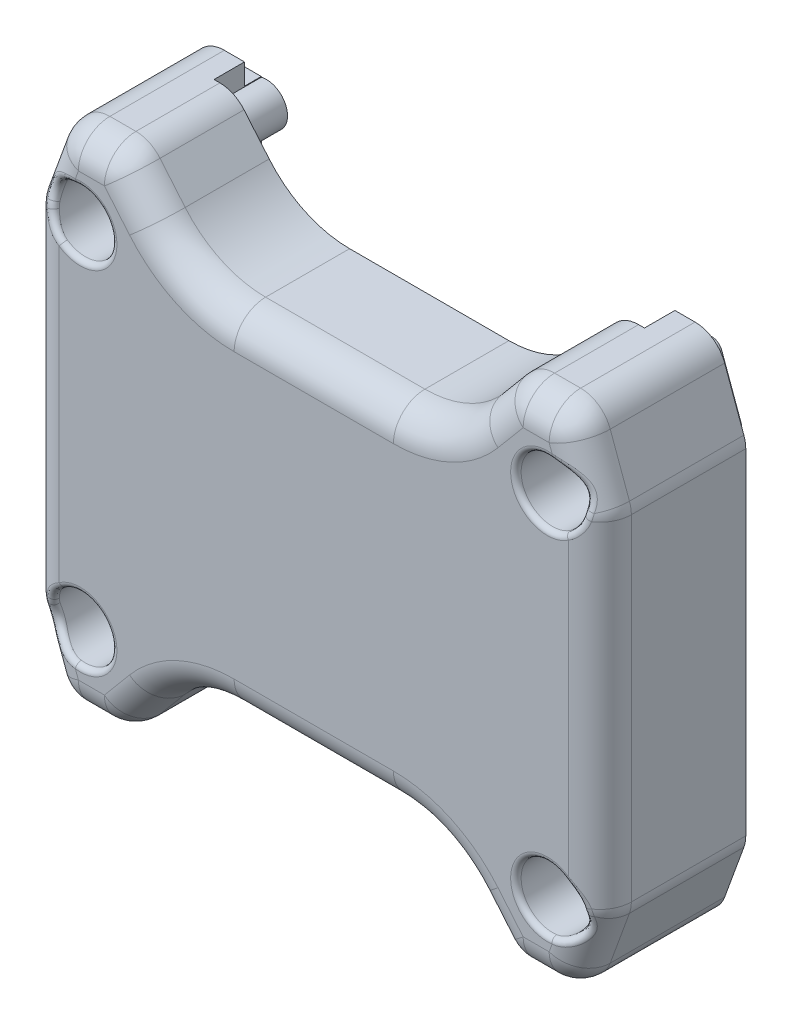
SolidWorks part; units mm, degrees
ref_plane "Alzado" through (0, 0, 0) normal (0, 0, 1) x (1, 0, 0)
ref_plane "Planta" through (0, 0, 0) normal (0, 1, 0) x (1, 0, 0)
ref_plane "Vista lateral" through (0, 0, 0) normal (1, 0, 0) x (0, 0, -1)
sketch "Croquis2" plane through (0, 0, 0) normal (0, 0, 1) x (1, 0, 0)
  line L0 (-20, 7.75) -> (-20, 15.75)
  line L1 (-20, -41.25) -> (20, -41.25)
  line L2 (-20, -41.25) -> (-20, -24.25)
  line L3 (-20, 38.75) -> (20, 38.75)
  line L4 (20, -41.25) -> (20, -24.25)
  line L5 (-20, 7.75) -> (5, 7.75)
  line L6 (-20, 4.75) -> (5, 4.75)
  line L7 (5, 7.75) -> (5, 4.75)
  line L8 (20, -10.25) -> (-5, -10.25)
  line L9 (20, -7.25) -> (-5, -7.25)
  line L10 (-5, -10.25) -> (-5, -7.25)
  line L11 (20, -7.25) -> (20, 15.75)
  line L12 (0, 38.75) -> (0, -41.25) construction
  line L14 (-20, 21.75) -> (-20, 38.75)
  line L15 (20, 21.75) -> (20, 38.75)
  line L16 (-20, -21.25) -> (20, -21.25) construction
  line L17 (-20, -18.25) -> (-20, 4.75)
  line L18 (20, -18.25) -> (20, -10.25)
  line L19 (0, 15.25) -> (0, -17.75) construction
  line L24 (27.25, -1.25) -> (-27.25, -1.25) construction
  line L29 (0, 15.25) -> (0, -17.75) construction
  line L39 (22.4196, 22.75) -> (21, 22.75)
  line L40 (21, 22.75) -> (21, 21.75)
  line L41 (21, 21.75) -> (22.4196, 21.75)
  line L42 (24.299, 20.434) -> (26.25, 15.0737)
  line L43 (26.25, 15.0737) -> (26.25, -17.5737)
  line L44 (26.25, -17.5737) -> (24.299, -22.934)
  line L45 (22.4196, -24.25) -> (21, -24.25)
  line L46 (21, -24.25) -> (21, -25.25)
  line L47 (21, -25.25) -> (22.4196, -25.25)
  line L48 (25.2387, -23.2761) -> (27.0691, -18.2471)
  line L49 (27.25, -17.221) -> (27.25, 14.721)
  line L50 (27.0691, 15.7471) -> (25.2387, 20.7761)
  line L51 (-22.4196, -25.25) -> (-21, -25.25)
  line L52 (-21, -25.25) -> (-21, -24.25)
  line L53 (-21, -24.25) -> (-22.4196, -24.25)
  line L54 (-24.299, -22.934) -> (-26.25, -17.5737)
  line L55 (-26.25, -17.5737) -> (-26.25, 15.0737)
  line L56 (-26.25, 15.0737) -> (-24.299, 20.434)
  line L57 (-22.4196, 21.75) -> (-21, 21.75)
  line L58 (-21, 21.75) -> (-21, 22.75)
  line L59 (-21, 22.75) -> (-22.4196, 22.75)
  line L60 (-25.2387, 20.7761) -> (-27.0691, 15.7471)
  line L61 (-27.25, 14.721) -> (-27.25, -17.221)
  line L62 (-27.0691, -18.2471) -> (-25.2387, -23.2761)
  line L63 (-21, 22.75) -> (-21, 21.75)
  line L64 (-21, 21.75) -> (-22.4196, 21.75)
  line L65 (-24.299, 20.434) -> (-26.25, 15.0737)
  line L66 (-26.25, 15.0737) -> (-26.25, -17.5737)
  line L67 (-26.25, -17.5737) -> (-24.299, -22.934)
  line L68 (-22.4196, -24.25) -> (-21, -24.25)
  line L69 (-21, -24.25) -> (-21, -25.25)
  line L70 (-21, -25.25) -> (-19.9422, -25.25)
  line L71 (-17.644, -24.1784) -> (-15.2474, -21.3221)
  line L72 (-7.5869, -17.75) -> (7.5869, -17.75)
  line L73 (15.2474, -21.3221) -> (17.644, -24.1784)
  line L74 (19.9422, -25.25) -> (21, -25.25)
  line L75 (21, -25.25) -> (21, -24.25)
  line L76 (21, -24.25) -> (22.4196, -24.25)
  line L77 (24.299, -22.934) -> (26.25, -17.5737)
  line L78 (26.25, -17.5737) -> (26.25, 15.0737)
  line L79 (26.25, 15.0737) -> (24.299, 20.434)
  line L80 (22.4196, 21.75) -> (21, 21.75)
  line L81 (21, 21.75) -> (21, 22.75)
  line L82 (21, 22.75) -> (19.9422, 22.75)
  line L83 (17.644, 21.6784) -> (15.2474, 18.8221)
  line L84 (7.5869, 15.25) -> (-7.5869, 15.25)
  line L85 (-15.2474, 18.8221) -> (-17.644, 21.6784)
  line L86 (-19.9422, 22.75) -> (-21, 22.75)
  line L87 (-20, -41.25) -> (20, -41.25)
  line L88 (-20, -41.25) -> (-20, -24.25)
  line L89 (-5, -10.25) -> (-5, -7.25)
  line L90 (20, -7.25) -> (-5, -7.25)
  line L91 (20, -10.25) -> (-5, -10.25)
  line L92 (5, 7.75) -> (5, 4.75)
  line L93 (-20, 4.75) -> (5, 4.75)
  line L94 (-20, 7.75) -> (5, 7.75)
  line L95 (-20, 7.75) -> (-20, 15.75)
  line L96 (20, -7.25) -> (20, 15.75)
  line L97 (20, -18.25) -> (20, -10.25)
  line L98 (20, -41.25) -> (20, -24.25)
  line L99 (-20, -18.25) -> (-20, 4.75)
  line L100 (-20, 21.75) -> (-20, 38.75)
  line L101 (-20, 38.75) -> (20, 38.75)
  line L102 (20, 21.75) -> (20, 38.75)
  line L103 (-27.0691, -18.2471) -> (-25.2387, -23.2761)
  line L104 (-27.25, 14.721) -> (-27.25, -17.221)
  line L105 (-25.2387, 20.7761) -> (-27.0691, 15.7471)
  line L106 (-21, 21.75) -> (-22.4196, 21.75)
  line L107 (-22.4196, -24.25) -> (-21, -24.25)
  line L108 (-21, -24.25) -> (-21, -25.25)
  line L109 (-21, 22.75) -> (-21, 21.75)
  line L110 (-26.25, 15.0737) -> (-26.25, -17.5737)
  line L111 (-24.299, 20.434) -> (-26.25, 15.0737)
  line L112 (-19.9422, 22.75) -> (-22.4196, 22.75)
  line L113 (-22.4196, -25.25) -> (-19.9422, -25.25)
  line L114 (-26.25, -17.5737) -> (-24.299, -22.934)
  line L115 (27.0691, 15.7471) -> (25.2387, 20.7761)
  line L116 (27.25, -17.221) -> (27.25, 14.721)
  line L117 (25.2387, -23.2761) -> (27.0691, -18.2471)
  line L118 (21, -24.25) -> (22.4196, -24.25)
  line L119 (26.25, 15.0737) -> (24.299, 20.434)
  line L120 (22.4196, 21.75) -> (21, 21.75)
  line L121 (21, 21.75) -> (21, 22.75)
  line L122 (21, -25.25) -> (21, -24.25)
  line L123 (22.4196, 22.75) -> (19.9422, 22.75)
  line L124 (26.25, -17.5737) -> (26.25, 15.0737)
  line L125 (24.299, -22.934) -> (26.25, -17.5737)
  line L126 (19.9422, -25.25) -> (22.4196, -25.25)
  line L127 (-17.644, 21.6784) -> (-15.2474, 18.8221)
  line L128 (7.5869, 15.25) -> (-7.5869, 15.25)
  line L129 (15.2474, 18.8221) -> (17.644, 21.6784)
  line L130 (17.644, -24.1784) -> (15.2474, -21.3221)
  line L131 (-7.5869, -17.75) -> (7.5869, -17.75)
  line L132 (-15.2474, -21.3221) -> (-17.644, -24.1784)
  line L133 (-25.25, 13.75) -> (-24.6867, 13.75)
  line L134 (19.8133, -16.25) -> (-19.8133, -16.25)
  line L135 (-19.8133, 13.75) -> (19.8133, 13.75)
  line L136 (24.6867, 13.75) -> (25.25, 13.75)
  line L137 (25.25, -16.25) -> (24.6867, -16.25)
  line L138 (-25.25, -16.25) -> (-25.25, 13.75)
  line L139 (-24.6867, -16.25) -> (-25.25, -16.25)
  line L140 (25.25, 13.75) -> (25.25, -16.25)
  line L141 (-25.25, -14) -> (-17.25, -14)
  line L142 (-17.25, -13) -> (-17.25, -16)
  line L143 (-17.25, -16) -> (-20.0139, -16)
  line L144 (-24.4861, -16) -> (-25.25, -16)
  line L145 (20.0139, -16) -> (17.25, -16)
  line L146 (17.25, -14) -> (25.25, -14)
  line L147 (17.25, -16) -> (17.25, -14)
  line L148 (25.25, -16) -> (24.4861, -16)
  line L149 (25.25, 11.5) -> (17.25, 11.5)
  line L150 (17.25, 13.5) -> (20.0139, 13.5)
  line L151 (17.25, 11.5) -> (17.25, 13.5)
  line L152 (24.4861, 13.5) -> (25.25, 13.5)
  line L153 (-17.25, 13.5) -> (-17.25, 10.5)
  line L154 (-20.0139, 13.5) -> (-17.25, 13.5)
  line L155 (-25.25, 13.5) -> (-24.4861, 13.5)
  line L156 (-17.25, 11.5) -> (-25.25, 11.5)
  line L157 (-24.25, 10.5) -> (-24.25, 6.5)
  line L158 (-24.25, 6.5) -> (-25.25, 6.5)
  line L159 (-17.25, 10.5) -> (-24.25, 10.5)
  line L160 (19.75, -13) -> (19.75, -14)
  line L161 (24.25, -13) -> (24.25, -9)
  line L162 (25.25, -9) -> (24.25, -9)
  line L163 (19.75, -13) -> (24.25, -13)
  line L164 (-24.25, -9) -> (-24.25, -13)
  line L165 (-24.25, -13) -> (-17.25, -13)
  line L166 (-25.25, -9) -> (-24.25, -9)
  line L167 (24.9375, 0.5) -> (24.9375, 2.5)
  line L168 (16, 13.75) -> (16, -16.25)
  line L169 (24.9375, 2.5) -> (25.25, 2.5)
  line L170 (-16, -16.25) -> (-16, 13.75)
  line L171 (24.9375, 0.5) -> (21.25, 0.5)
  line L172 (21.25, 0.5) -> (21.25, 11.5)
  line L173 (13.5, -11.25) -> (13.5, -6.25)
  line L174 (13.5, -6.25) -> (15.5, -6.25)
  line L175 (15.5, -6.25) -> (15.5, -13.25)
  line L176 (15.5, -13.25) -> (8, -13.25)
  line L177 (8, -13.25) -> (8, -11.25)
  line L178 (8, -11.25) -> (13.5, -11.25)
  line L179 (-13.5, 3.25) -> (-15.5, 3.25)
  line L180 (-15.5, 3.25) -> (-15.5, 10.25)
  line L181 (-15.5, 10.25) -> (-8, 10.25)
  line L182 (-8, 10.25) -> (-8, 8.25)
  line L183 (-8, 8.25) -> (-13.5, 8.25)
  line L184 (-13.5, 8.25) -> (-13.5, 3.25)
  line L185 (-13.5, -11.25) -> (-8, -11.25)
  line L186 (-8, -11.25) -> (-8, -13.25)
  line L187 (-8, -13.25) -> (-15.5, -13.25)
  line L188 (-15.5, -13.25) -> (-15.5, -6.25)
  line L189 (-15.5, -6.25) -> (-13.5, -6.25)
  line L190 (-13.5, -6.25) -> (-13.5, -11.25)
  line L191 (8, 10.25) -> (15.5, 10.25)
  line L192 (13.5, 3.25) -> (13.5, 8.25)
  line L193 (13.5, 8.25) -> (8, 8.25)
  line L194 (8, 8.25) -> (8, 10.25)
  line L195 (15.5, 10.25) -> (15.5, 3.25)
  line L196 (15.5, 3.25) -> (13.5, 3.25)
  line L197 (-12.5, -3.75) -> (-12.5, 4.625)
  line L198 (10.5, -5.75) -> (-10.5, -5.75)
  line L199 (12.5, 4.625) -> (12.5, -3.75)
  line L200 (-10.5, 6.625) -> (10.5, 6.625)
  circle A0 centre (0, 24.75) radius 8
  circle A1 centre (0, -27.25) radius 8
  arc A2 (-20, 15.75) -> (-20, 21.75) centre (-20, 18.75) ccw
  arc A3 (20, 21.75) -> (20, 15.75) centre (20, 18.75) ccw
  arc A4 (-20, -24.25) -> (-20, -18.25) centre (-20, -21.25) ccw
  arc A5 (20, -18.25) -> (20, -24.25) centre (20, -21.25) ccw
  circle A6 centre (-20, 18.75) radius 2
  circle A7 centre (20, 18.75) radius 2
  circle A8 centre (20, -21.25) radius 2
  circle A9 centre (-20, -21.25) radius 2
  circle A10 centre (-22.25, -18) radius 1.5
  circle A11 centre (-22.25, -18) radius 3
  circle A12 centre (20, -21.25) radius 2
  circle A13 centre (22.25, -18) radius 1.5
  circle A14 centre (22.25, -18) radius 3
  circle A15 centre (22.25, 15.5) radius 3
  circle A16 centre (22.25, 15.5) radius 1.5
  circle A17 centre (-22.25, 15.5) radius 3
  circle A18 centre (-22.25, 15.5) radius 1.5
  arc A19 (24.299, 20.434) -> (22.4196, 21.75) centre (22.4196, 19.75) ccw
  arc A20 (22.4196, -24.25) -> (24.299, -22.934) centre (22.4196, -22.25) ccw
  arc A21 (22.4196, -25.25) -> (25.2387, -23.2761) centre (22.4196, -22.25) ccw
  arc A22 (27.0691, -18.2471) -> (27.25, -17.221) centre (24.25, -17.221) ccw
  arc A23 (27.25, 14.721) -> (27.0691, 15.7471) centre (24.25, 14.721) ccw
  arc A24 (25.2387, 20.7761) -> (22.4196, 22.75) centre (22.4196, 19.75) ccw
  arc A25 (-24.299, -22.934) -> (-22.4196, -24.25) centre (-22.4196, -22.25) ccw
  arc A26 (-22.4196, 21.75) -> (-24.299, 20.434) centre (-22.4196, 19.75) ccw
  arc A27 (-22.4196, 22.75) -> (-25.2387, 20.7761) centre (-22.4196, 19.75) ccw
  arc A28 (-27.0691, 15.7471) -> (-27.25, 14.721) centre (-24.25, 14.721) ccw
  arc A29 (-27.25, -17.221) -> (-27.0691, -18.2471) centre (-24.25, -17.221) ccw
  arc A30 (-25.2387, -23.2761) -> (-22.4196, -25.25) centre (-22.4196, -22.25) ccw
  arc A31 (-22.4196, 21.75) -> (-24.299, 20.434) centre (-22.4196, 19.75) ccw
  arc A32 (-24.299, -22.934) -> (-22.4196, -24.25) centre (-22.4196, -22.25) ccw
  arc A33 (-19.9422, -25.25) -> (-17.644, -24.1784) centre (-19.9422, -22.25) ccw
  arc A34 (-7.5869, -17.75) -> (-15.2474, -21.3221) centre (-7.5869, -27.75) ccw
  arc A35 (15.2474, -21.3221) -> (7.5869, -17.75) centre (7.5869, -27.75) ccw
  arc A36 (17.644, -24.1784) -> (19.9422, -25.25) centre (19.9422, -22.25) ccw
  arc A37 (22.4196, -24.25) -> (24.299, -22.934) centre (22.4196, -22.25) ccw
  arc A38 (24.299, 20.434) -> (22.4196, 21.75) centre (22.4196, 19.75) ccw
  arc A39 (19.9422, 22.75) -> (17.644, 21.6784) centre (19.9422, 19.75) ccw
  arc A40 (7.5869, 15.25) -> (15.2474, 18.8221) centre (7.5869, 25.25) ccw
  arc A41 (-15.2474, 18.8221) -> (-7.5869, 15.25) centre (-7.5869, 25.25) ccw
  arc A42 (-17.644, 21.6784) -> (-19.9422, 22.75) centre (-19.9422, 19.75) ccw
  circle A43 centre (0, -27.25) radius 8
  circle A44 centre (0, 24.75) radius 8
  arc A45 (-20, 15.75) -> (-20, 21.75) centre (-20, 18.75) ccw
  arc A46 (20, -18.25) -> (20, -24.25) centre (20, -21.25) ccw
  arc A47 (-20, -24.25) -> (-20, -18.25) centre (-20, -21.25) ccw
  arc A48 (20, 21.75) -> (20, 15.75) centre (20, 18.75) ccw
  circle A49 centre (-20, -21.25) radius 2
  circle A50 centre (20, -21.25) radius 2
  circle A51 centre (20, 18.75) radius 2
  circle A52 centre (-20, 18.75) radius 2
  circle A53 centre (22.25, 15.5) radius 1.5
  circle A54 centre (22.25, -18) radius 1.5
  circle A55 centre (-22.25, -18) radius 1.5
  circle A56 centre (-22.25, 15.5) radius 1.5
  arc A57 (-22.4196, 22.75) -> (-25.2387, 20.7761) centre (-22.4196, 19.75) ccw
  arc A58 (-24.299, -22.934) -> (-22.4196, -24.25) centre (-22.4196, -22.25) ccw
  arc A59 (-27.25, -17.221) -> (-27.0691, -18.2471) centre (-24.25, -17.221) ccw
  arc A60 (-25.2387, -23.2761) -> (-22.4196, -25.25) centre (-22.4196, -22.25) ccw
  arc A61 (-27.0691, 15.7471) -> (-27.25, 14.721) centre (-24.25, 14.721) ccw
  arc A62 (-22.4196, 21.75) -> (-24.299, 20.434) centre (-22.4196, 19.75) ccw
  arc A63 (27.25, 14.721) -> (27.0691, 15.7471) centre (24.25, 14.721) ccw
  arc A64 (27.0691, -18.2471) -> (27.25, -17.221) centre (24.25, -17.221) ccw
  arc A65 (22.4196, -24.25) -> (24.299, -22.934) centre (22.4196, -22.25) ccw
  arc A66 (24.299, 20.434) -> (22.4196, 21.75) centre (22.4196, 19.75) ccw
  arc A67 (25.2387, 20.7761) -> (22.4196, 22.75) centre (22.4196, 19.75) ccw
  arc A68 (22.4196, -25.25) -> (25.2387, -23.2761) centre (22.4196, -22.25) ccw
  arc A69 (-17.644, 21.6784) -> (-19.9422, 22.75) centre (-19.9422, 19.75) ccw
  arc A70 (-15.2474, 18.8221) -> (-7.5869, 15.25) centre (-7.5869, 25.25) ccw
  arc A71 (7.5869, 15.25) -> (15.2474, 18.8221) centre (7.5869, 25.25) ccw
  arc A72 (19.9422, 22.75) -> (17.644, 21.6784) centre (19.9422, 19.75) ccw
  arc A73 (17.644, -24.1784) -> (19.9422, -25.25) centre (19.9422, -22.25) ccw
  arc A74 (15.2474, -21.3221) -> (7.5869, -17.75) centre (7.5869, -27.75) ccw
  arc A75 (-7.5869, -17.75) -> (-15.2474, -21.3221) centre (-7.5869, -27.75) ccw
  arc A76 (-19.9422, -25.25) -> (-17.644, -24.1784) centre (-19.9422, -22.25) ccw
  arc A77 (-19.8133, -16.25) -> (-24.6867, -16.25) centre (-22.25, -18) ccw
  arc A78 (24.6867, -16.25) -> (19.8133, -16.25) centre (22.25, -18) ccw
  arc A79 (19.8133, 13.75) -> (24.6867, 13.75) centre (22.25, 15.5) ccw
  arc A80 (-24.6867, 13.75) -> (-19.8133, 13.75) centre (-22.25, 15.5) ccw
  arc A81 (-10.5, 6.625) -> (-12.5, 4.625) centre (-10.5, 4.625) ccw
  arc A82 (-12.5, -3.75) -> (-10.5, -5.75) centre (-10.5, -3.75) ccw
  arc A83 (10.5, -5.75) -> (12.5, -3.75) centre (10.5, -3.75) ccw
  arc A84 (12.5, 4.625) -> (10.5, 6.625) centre (10.5, 4.625) ccw
  point P146 (0, -1.25)
sketch "Croquis3" plane through (0, 0, 0) normal (0, 0, 1) x (1, 0, 0)
  line L0 (15.2474, -21.3221) -> (17.644, -24.1784) construction
  line L1 (-21, 22.75) -> (-22.4196, 22.75) construction
  line L2 (-25.2387, 20.7761) -> (-27.0691, 15.7471) construction
  line L3 (-27.25, 14.721) -> (-27.25, -17.221) construction
  line L4 (-27.0691, -18.2471) -> (-25.2387, -23.2761) construction
  line L5 (-22.4196, -25.25) -> (-21, -25.25) construction
  line L6 (-21, -25.25) -> (-19.9422, -25.25) construction
  line L7 (-17.644, -24.1784) -> (-15.2474, -21.3221) construction
  line L8 (-7.5869, -17.75) -> (7.5869, -17.75) construction
  line L9 (22.4196, 22.75) -> (21, 22.75) construction
  line L10 (-21, -25.25) -> (-19.9422, -25.25)
  line L11 (-19.9422, 22.75) -> (-21, 22.75) construction
  line L12 (-15.2474, 18.8221) -> (-17.644, 21.6784) construction
  line L13 (7.5869, 15.25) -> (-7.5869, 15.25) construction
  line L14 (17.644, 21.6784) -> (15.2474, 18.8221) construction
  line L15 (21, 22.75) -> (19.9422, 22.75) construction
  line L16 (27.0691, 15.7471) -> (25.2387, 20.7761) construction
  line L17 (19.9422, -25.25) -> (21, -25.25) construction
  line L18 (21, -25.25) -> (22.4196, -25.25) construction
  line L19 (25.2387, -23.2761) -> (27.0691, -18.2471) construction
  line L20 (27.25, -17.221) -> (27.25, 14.721) construction
  line L21 (19.9422, -25.25) -> (21, -25.25)
  line L22 (21, -25.25) -> (22.4196, -25.25)
  line L23 (25.2387, -23.2761) -> (27.0691, -18.2471)
  line L24 (27.25, -17.221) -> (27.25, 14.721)
  line L25 (27.0691, 15.7471) -> (25.2387, 20.7761)
  line L26 (22.4196, 22.75) -> (21, 22.75)
  line L27 (21, 22.75) -> (19.9422, 22.75)
  line L28 (17.644, 21.6784) -> (15.2474, 18.8221)
  line L29 (7.5869, 15.25) -> (-7.5869, 15.25)
  line L30 (-15.2474, 18.8221) -> (-17.644, 21.6784)
  line L31 (-19.9422, 22.75) -> (-21, 22.75)
  line L32 (-21, 22.75) -> (-22.4196, 22.75)
  line L33 (-25.2387, 20.7761) -> (-27.0691, 15.7471)
  line L34 (-27.25, 14.721) -> (-27.25, -17.221)
  line L35 (-27.0691, -18.2471) -> (-25.2387, -23.2761)
  line L36 (21.25, 0.5) -> (21.25, 11.5) construction
  line L37 (-22.4196, -25.25) -> (-21, -25.25)
  line L38 (-17.644, -24.1784) -> (-15.2474, -21.3221)
  line L39 (-7.5869, -17.75) -> (7.5869, -17.75)
  line L40 (15.2474, -21.3221) -> (17.644, -24.1784)
  line L41 (-24.25, -14.75) -> (21.25, -14.75)
  line L42 (-24.25, -14.75) -> (-24.25, 12.25)
  line L43 (-24.25, 12.25) -> (21.25, 12.25)
  line L44 (21.25, -14.75) -> (21.25, 12.25)
  arc A0 (-22.4196, 22.75) -> (-25.2387, 20.7761) centre (-22.4196, 19.75) ccw construction
  arc A1 (-27.0691, 15.7471) -> (-27.25, 14.721) centre (-24.25, 14.721) ccw construction
  arc A2 (-27.25, -17.221) -> (-27.0691, -18.2471) centre (-24.25, -17.221) ccw construction
  arc A3 (-25.2387, -23.2761) -> (-22.4196, -25.25) centre (-22.4196, -22.25) ccw construction
  arc A4 (-19.9422, -25.25) -> (-17.644, -24.1784) centre (-19.9422, -22.25) ccw construction
  arc A5 (-7.5869, -17.75) -> (-15.2474, -21.3221) centre (-7.5869, -27.75) ccw construction
  arc A6 (15.2474, -21.3221) -> (7.5869, -17.75) centre (7.5869, -27.75) ccw construction
  arc A7 (17.644, -24.1784) -> (19.9422, -25.25) centre (19.9422, -22.25) ccw construction
  arc A8 (-17.644, 21.6784) -> (-19.9422, 22.75) centre (-19.9422, 19.75) ccw construction
  arc A9 (-15.2474, 18.8221) -> (-7.5869, 15.25) centre (-7.5869, 25.25) ccw construction
  arc A10 (7.5869, 15.25) -> (15.2474, 18.8221) centre (7.5869, 25.25) ccw construction
  arc A11 (19.9422, 22.75) -> (17.644, 21.6784) centre (19.9422, 19.75) ccw construction
  arc A12 (25.2387, 20.7761) -> (22.4196, 22.75) centre (22.4196, 19.75) ccw construction
  arc A13 (22.4196, -25.25) -> (25.2387, -23.2761) centre (22.4196, -22.25) ccw construction
  arc A14 (27.0691, -18.2471) -> (27.25, -17.221) centre (24.25, -17.221) ccw construction
  arc A15 (27.25, 14.721) -> (27.0691, 15.7471) centre (24.25, 14.721) ccw construction
  arc A16 (22.4196, -25.25) -> (25.2387, -23.2761) centre (22.4196, -22.25) ccw
  arc A17 (27.0691, -18.2471) -> (27.25, -17.221) centre (24.25, -17.221) ccw
  arc A18 (27.25, 14.721) -> (27.0691, 15.7471) centre (24.25, 14.721) ccw
  arc A19 (25.2387, 20.7761) -> (22.4196, 22.75) centre (22.4196, 19.75) ccw
  arc A20 (19.9422, 22.75) -> (17.644, 21.6784) centre (19.9422, 19.75) ccw
  arc A21 (7.5869, 15.25) -> (15.2474, 18.8221) centre (7.5869, 25.25) ccw
  arc A22 (-15.2474, 18.8221) -> (-7.5869, 15.25) centre (-7.5869, 25.25) ccw
  arc A23 (-17.644, 21.6784) -> (-19.9422, 22.75) centre (-19.9422, 19.75) ccw
  arc A24 (-22.4196, 22.75) -> (-25.2387, 20.7761) centre (-22.4196, 19.75) ccw
  arc A25 (-27.0691, 15.7471) -> (-27.25, 14.721) centre (-24.25, 14.721) ccw
  arc A26 (-27.25, -17.221) -> (-27.0691, -18.2471) centre (-24.25, -17.221) ccw
  arc A27 (-25.2387, -23.2761) -> (-22.4196, -25.25) centre (-22.4196, -22.25) ccw
  arc A28 (-19.9422, -25.25) -> (-17.644, -24.1784) centre (-19.9422, -22.25) ccw
  arc A29 (-7.5869, -17.75) -> (-15.2474, -21.3221) centre (-7.5869, -27.75) ccw
  arc A30 (15.2474, -21.3221) -> (7.5869, -17.75) centre (7.5869, -27.75) ccw
  arc A31 (17.644, -24.1784) -> (19.9422, -25.25) centre (19.9422, -22.25) ccw
  dimension "D1" = 3
  dimension "D2" = 3
  dimension "D3" = 6
  dimension "D4" = 3
extrude "Saliente-Extruir1" add sketch "Croquis3" along normal blind 9
sketch "Croquis4" plane through (0, 0, 9) normal (0, 0, 1) x (1, 0, 0)
  line L16 (19.9422, -25.25) -> (22.4196, -25.25)
  line L17 (25.2387, -23.2761) -> (27.0691, -18.2471)
  line L18 (27.25, -17.221) -> (27.25, 14.721)
  line L19 (27.0691, 15.7471) -> (25.2387, 20.7761)
  line L20 (22.4196, 22.75) -> (19.9422, 22.75)
  line L21 (17.644, 21.6784) -> (15.2474, 18.8221)
  line L22 (7.5869, 15.25) -> (-7.5869, 15.25)
  line L23 (-15.2474, 18.8221) -> (-17.644, 21.6784)
  line L24 (-19.9422, 22.75) -> (-22.4196, 22.75)
  line L25 (-25.2387, 20.7761) -> (-27.0691, 15.7471)
  line L26 (-27.25, 14.721) -> (-27.25, -17.221)
  line L27 (-27.0691, -18.2471) -> (-25.2387, -23.2761)
  line L28 (-22.4196, -25.25) -> (-19.9422, -25.25)
  line L29 (-17.644, -24.1784) -> (-15.2474, -21.3221)
  line L30 (-7.5869, -17.75) -> (7.5869, -17.75)
  line L31 (15.2474, -21.3221) -> (17.644, -24.1784)
  line L32 (19.9422, -25.25) -> (22.4196, -25.25)
  line L33 (25.2387, -23.2761) -> (27.0691, -18.2471)
  line L34 (27.25, -17.221) -> (27.25, 14.721)
  line L35 (27.0691, 15.7471) -> (25.2387, 20.7761)
  line L36 (22.4196, 22.75) -> (19.9422, 22.75)
  line L37 (17.644, 21.6784) -> (15.2474, 18.8221)
  line L38 (7.5869, 15.25) -> (-7.5869, 15.25)
  line L39 (-15.2474, 18.8221) -> (-17.644, 21.6784)
  line L40 (-19.9422, 22.75) -> (-22.4196, 22.75)
  line L41 (-25.2387, 20.7761) -> (-27.0691, 15.7471)
  line L42 (-27.25, 14.721) -> (-27.25, -17.221)
  line L43 (-27.0691, -18.2471) -> (-25.2387, -23.2761)
  line L44 (-22.4196, -25.25) -> (-19.9422, -25.25)
  line L45 (-17.644, -24.1784) -> (-15.2474, -21.3221)
  line L46 (-7.5869, -17.75) -> (7.5869, -17.75)
  line L47 (15.2474, -21.3221) -> (17.644, -24.1784)
  arc A16 (17.644, -24.1784) -> (19.9422, -25.25) centre (19.9422, -22.25) ccw
  arc A17 (22.4196, -25.25) -> (25.2387, -23.2761) centre (22.4196, -22.25) ccw
  arc A18 (27.0691, -18.2471) -> (27.25, -17.221) centre (24.25, -17.221) ccw
  arc A19 (27.25, 14.721) -> (27.0691, 15.7471) centre (24.25, 14.721) ccw
  arc A20 (25.2387, 20.7761) -> (22.4196, 22.75) centre (22.4196, 19.75) ccw
  arc A21 (19.9422, 22.75) -> (17.644, 21.6784) centre (19.9422, 19.75) ccw
  arc A22 (7.5869, 15.25) -> (15.2474, 18.8221) centre (7.5869, 25.25) ccw
  arc A23 (-15.2474, 18.8221) -> (-7.5869, 15.25) centre (-7.5869, 25.25) ccw
  arc A24 (-17.644, 21.6784) -> (-19.9422, 22.75) centre (-19.9422, 19.75) ccw
  arc A25 (-22.4196, 22.75) -> (-25.2387, 20.7761) centre (-22.4196, 19.75) ccw
  arc A26 (-27.0691, 15.7471) -> (-27.25, 14.721) centre (-24.25, 14.721) ccw
  arc A27 (-27.25, -17.221) -> (-27.0691, -18.2471) centre (-24.25, -17.221) ccw
  arc A28 (-25.2387, -23.2761) -> (-22.4196, -25.25) centre (-22.4196, -22.25) ccw
  arc A29 (-19.9422, -25.25) -> (-17.644, -24.1784) centre (-19.9422, -22.25) ccw
  arc A30 (-7.5869, -17.75) -> (-15.2474, -21.3221) centre (-7.5869, -27.75) ccw
  arc A31 (15.2474, -21.3221) -> (7.5869, -17.75) centre (7.5869, -27.75) ccw
  arc A32 (17.644, -24.1784) -> (19.9422, -25.25) centre (19.9422, -22.25) ccw
  arc A33 (22.4196, -25.25) -> (25.2387, -23.2761) centre (22.4196, -22.25) ccw
  arc A34 (27.0691, -18.2471) -> (27.25, -17.221) centre (24.25, -17.221) ccw
  arc A35 (27.25, 14.721) -> (27.0691, 15.7471) centre (24.25, 14.721) ccw
  arc A36 (25.2387, 20.7761) -> (22.4196, 22.75) centre (22.4196, 19.75) ccw
  arc A37 (19.9422, 22.75) -> (17.644, 21.6784) centre (19.9422, 19.75) ccw
  arc A38 (7.5869, 15.25) -> (15.2474, 18.8221) centre (7.5869, 25.25) ccw
  arc A39 (-15.2474, 18.8221) -> (-7.5869, 15.25) centre (-7.5869, 25.25) ccw
  arc A40 (-17.644, 21.6784) -> (-19.9422, 22.75) centre (-19.9422, 19.75) ccw
  arc A41 (-22.4196, 22.75) -> (-25.2387, 20.7761) centre (-22.4196, 19.75) ccw
  arc A42 (-27.0691, 15.7471) -> (-27.25, 14.721) centre (-24.25, 14.721) ccw
  arc A43 (-27.25, -17.221) -> (-27.0691, -18.2471) centre (-24.25, -17.221) ccw
  arc A44 (-25.2387, -23.2761) -> (-22.4196, -25.25) centre (-22.4196, -22.25) ccw
  arc A45 (-19.9422, -25.25) -> (-17.644, -24.1784) centre (-19.9422, -22.25) ccw
  arc A46 (-7.5869, -17.75) -> (-15.2474, -21.3221) centre (-7.5869, -27.75) ccw
  arc A47 (15.2474, -21.3221) -> (7.5869, -17.75) centre (7.5869, -27.75) ccw
  dimension "D1" = 0
extrude "Saliente-Extruir2" add sketch "Croquis4" along normal blind 2
sketch "Croquis5" plane through (0, 0, 0) normal (0, 0, -1) x (-1, 0, 0)
  circle A0 centre (-20, -21.25) radius 2 construction
  circle A1 centre (20, -21.25) radius 2 construction
  circle A2 centre (20, 18.75) radius 2 construction
  circle A3 centre (-20, 18.75) radius 2 construction
  circle A4 centre (-20, -21.25) radius 2 construction
  circle A5 centre (20, -21.25) radius 2 construction
  circle A6 centre (20, 18.75) radius 2
  circle A7 centre (-20, 18.75) radius 2
  circle A8 centre (-20, -21.25) radius 2.5
  circle A9 centre (20, -21.25) radius 2.5
  dimension "D1" = 5
  dimension "D2" = 5
extrude "Saliente-Extruir3" add sketch "Croquis5" along normal blind 4.5
sketch "Croquis6" plane through (0, 0, 0) normal (0, 0, -1) x (-1, 0, 0)
  line L0 (-20, -25.25) -> (-20, -23.25)
  line L1 (-20, -41.25) -> (-20, -24.25) construction
  line L2 (20, -41.25) -> (20, -24.25) construction
  line L3 (20, -25.25) -> (20, -23.25)
  line L4 (-20.5, 16.8135) -> (-20.5, 12.25)
  line L5 (20.5, 16.8135) -> (20.5, 12.25)
  line L6 (-20.5, 22.75) -> (-20.5, 20.6865)
  line L7 (20.5, 22.75) -> (20.5, 20.6865)
  line L8 (-20, 21.75) -> (-20, 38.75) construction
  line L9 (20, 21.75) -> (20, 38.75) construction
  line L10 (-21.25, -14.75) -> (-21.25, 12.25) construction
  line L11 (24.25, -14.75) -> (-21.25, -14.75) construction
  line L12 (24.25, 12.25) -> (24.25, -14.75) construction
  line L13 (-21.25, 12.25) -> (24.25, 12.25) construction
  line L14 (24.25, -14.75) -> (20, -14.75)
  line L15 (24.25, 12.25) -> (24.25, -14.75)
  line L16 (-17.644, -24.1784) -> (-15.2474, -21.3221)
  line L17 (-7.5869, -17.75) -> (7.5869, -17.75)
  line L18 (15.2474, -21.3221) -> (17.644, -24.1784)
  line L19 (19.9422, -25.25) -> (22.4196, -25.25)
  line L20 (25.2387, -23.2761) -> (27.0691, -18.2471)
  line L21 (27.25, -17.221) -> (27.25, 14.721)
  line L22 (27.0691, 15.7471) -> (25.2387, 20.7761)
  line L23 (22.4196, 22.75) -> (19.9422, 22.75)
  line L24 (17.644, 21.6784) -> (15.2474, 18.8221)
  line L25 (7.5869, 15.25) -> (-7.5869, 15.25)
  line L26 (-15.2474, 18.8221) -> (-17.644, 21.6784)
  line L27 (-19.9422, 22.75) -> (-22.4196, 22.75)
  line L28 (-25.2387, 20.7761) -> (-27.0691, 15.7471)
  line L29 (-27.25, 14.721) -> (-27.25, -17.221)
  line L30 (-27.0691, -18.2471) -> (-25.2387, -23.2761)
  line L31 (-22.4196, -25.25) -> (-19.9422, -25.25)
  line L35 (20, -25.25) -> (22.4196, -25.25)
  line L36 (25.2387, -23.2761) -> (27.0691, -18.2471)
  line L37 (27.25, -17.221) -> (27.25, 14.721)
  line L38 (27.0691, 15.7471) -> (25.2387, 20.7761)
  line L39 (22.4196, 22.75) -> (20.5, 22.75)
  line L43 (-20.5, 22.75) -> (-22.4196, 22.75)
  line L44 (-25.2387, 20.7761) -> (-27.0691, 15.7471)
  line L45 (-27.25, 14.721) -> (-27.25, -17.221)
  line L46 (-27.0691, -18.2471) -> (-25.2387, -23.2761)
  line L47 (-22.4196, -25.25) -> (-20, -25.25)
  line L48 (-21.25, 12.25) -> (-20.5, 12.25)
  line L49 (-21.25, -14.75) -> (-21.25, 12.25)
  line L50 (20.5, 12.25) -> (24.25, 12.25)
  line L51 (-20, -14.75) -> (-21.25, -14.75)
  line L52 (20, -19.25) -> (20, -14.75)
  line L53 (-20, -19.25) -> (-20, -14.75)
  circle A0 centre (-20, -21.25) radius 2 construction
  circle A1 centre (20, -21.25) radius 2 construction
  circle A2 centre (20, 18.75) radius 2 construction
  circle A3 centre (-20, 18.75) radius 2 construction
  arc A4 (-20, -23.25) -> (-20, -19.25) centre (-20, -21.25) ccw
  arc A5 (20, -19.25) -> (20, -23.25) centre (20, -21.25) ccw
  arc A6 (20.5, 20.6865) -> (20.5, 16.8135) centre (20, 18.75) ccw
  arc A7 (-20.5, 16.8135) -> (-20.5, 20.6865) centre (-20, 18.75) ccw
  arc A16 (-19.9422, -25.25) -> (-17.644, -24.1784) centre (-19.9422, -22.25) ccw
  arc A17 (-7.5869, -17.75) -> (-15.2474, -21.3221) centre (-7.5869, -27.75) ccw
  arc A18 (15.2474, -21.3221) -> (7.5869, -17.75) centre (7.5869, -27.75) ccw
  arc A19 (17.644, -24.1784) -> (19.9422, -25.25) centre (19.9422, -22.25) ccw
  arc A20 (22.4196, -25.25) -> (25.2387, -23.2761) centre (22.4196, -22.25) ccw
  arc A21 (27.0691, -18.2471) -> (27.25, -17.221) centre (24.25, -17.221) ccw
  arc A22 (27.25, 14.721) -> (27.0691, 15.7471) centre (24.25, 14.721) ccw
  arc A23 (25.2387, 20.7761) -> (22.4196, 22.75) centre (22.4196, 19.75) ccw
  arc A24 (19.9422, 22.75) -> (17.644, 21.6784) centre (19.9422, 19.75) ccw
  arc A25 (7.5869, 15.25) -> (15.2474, 18.8221) centre (7.5869, 25.25) ccw
  arc A26 (-15.2474, 18.8221) -> (-7.5869, 15.25) centre (-7.5869, 25.25) ccw
  arc A27 (-17.644, 21.6784) -> (-19.9422, 22.75) centre (-19.9422, 19.75) ccw
  arc A28 (-22.4196, 22.75) -> (-25.2387, 20.7761) centre (-22.4196, 19.75) ccw
  arc A29 (-27.0691, 15.7471) -> (-27.25, 14.721) centre (-24.25, 14.721) ccw
  arc A30 (-27.25, -17.221) -> (-27.0691, -18.2471) centre (-24.25, -17.221) ccw
  arc A31 (-25.2387, -23.2761) -> (-22.4196, -25.25) centre (-22.4196, -22.25) ccw
  arc A36 (22.4196, -25.25) -> (25.2387, -23.2761) centre (22.4196, -22.25) ccw
  arc A37 (27.0691, -18.2471) -> (27.25, -17.221) centre (24.25, -17.221) ccw
  arc A38 (27.25, 14.721) -> (27.0691, 15.7471) centre (24.25, 14.721) ccw
  arc A39 (25.2387, 20.7761) -> (22.4196, 22.75) centre (22.4196, 19.75) ccw
  arc A44 (-22.4196, 22.75) -> (-25.2387, 20.7761) centre (-22.4196, 19.75) ccw
  arc A45 (-27.0691, 15.7471) -> (-27.25, 14.721) centre (-24.25, 14.721) ccw
  arc A46 (-27.25, -17.221) -> (-27.0691, -18.2471) centre (-24.25, -17.221) ccw
  arc A47 (-25.2387, -23.2761) -> (-22.4196, -25.25) centre (-22.4196, -22.25) ccw
  dimension "D2" = 0.5
  dimension "D3" = 0.5
  dimension "D1" = 0
extrude "Saliente-Extruir4" add sketch "Croquis6" along normal blind 4.5
sketch "Croquis8" plane through (0, 0, -4.5) normal (0, 0, -1) x (-1, 0, 0)
  line L0 (-20.5, 20.75) -> (-20.5, 22.75)
  line L1 (20, -25.25) -> (22.4196, -25.25) construction
  line L2 (25.2387, -23.2761) -> (27.0691, -18.2471) construction
  line L3 (27.25, -17.221) -> (27.25, 14.721) construction
  line L4 (27.0691, 15.7471) -> (25.2387, 20.7761) construction
  line L5 (22.4196, 22.75) -> (20.5, 22.75) construction
  line L6 (-20, -25.25) -> (-20, -23.25)
  line L7 (20, -25.25) -> (20, -23.25)
  line L8 (20.5, 20.75) -> (20.5, 22.75)
  line L18 (-20.5, 22.75) -> (-22.4196, 22.75) construction
  line L19 (-25.2387, 20.7761) -> (-27.0691, 15.7471) construction
  line L20 (-27.25, 14.721) -> (-27.25, -17.221) construction
  line L21 (-27.0691, -18.2471) -> (-25.2387, -23.2761) construction
  line L22 (-22.4196, -25.25) -> (-20, -25.25) construction
  line L25 (20, -25.25) -> (22.4196, -25.25)
  line L26 (25.2387, -23.2761) -> (27.0691, -18.2471)
  line L27 (27.25, -17.221) -> (27.25, 14.721)
  line L28 (27.0691, 15.7471) -> (25.2387, 20.7761)
  line L29 (22.4196, 22.75) -> (20.5, 22.75)
  line L42 (-20.5, 22.75) -> (-22.4196, 22.75)
  line L43 (-25.2387, 20.7761) -> (-27.0691, 15.7471)
  line L44 (-27.25, 14.721) -> (-27.25, -17.221)
  line L45 (-27.0691, -18.2471) -> (-25.2387, -23.2761)
  line L46 (-22.4196, -25.25) -> (-20, -25.25)
  line L48 (20, -23.25) -> (22.4196, -23.25)
  line L49 (23.3593, -22.592) -> (25.1897, -17.563)
  line L50 (25.25, -17.221) -> (25.25, 14.721)
  line L51 (25.1897, 15.063) -> (23.3593, 20.092)
  line L52 (22.4196, 20.75) -> (20.5, 20.75)
  line L53 (-20.5, 20.75) -> (-22.4196, 20.75)
  line L54 (-23.3593, 20.092) -> (-25.1897, 15.063)
  line L55 (-25.25, 14.721) -> (-25.25, -17.221)
  line L56 (-25.1897, -17.563) -> (-23.3593, -22.592)
  line L57 (-22.4196, -23.25) -> (-20, -23.25)
  arc A1 (22.4196, -25.25) -> (25.2387, -23.2761) centre (22.4196, -22.25) ccw construction
  arc A2 (27.0691, -18.2471) -> (27.25, -17.221) centre (24.25, -17.221) ccw construction
  arc A3 (27.25, 14.721) -> (27.0691, 15.7471) centre (24.25, 14.721) ccw construction
  arc A4 (25.2387, 20.7761) -> (22.4196, 22.75) centre (22.4196, 19.75) ccw construction
  arc A8 (-22.4196, 22.75) -> (-25.2387, 20.7761) centre (-22.4196, 19.75) ccw construction
  arc A9 (-27.0691, 15.7471) -> (-27.25, 14.721) centre (-24.25, 14.721) ccw construction
  arc A10 (-27.25, -17.221) -> (-27.0691, -18.2471) centre (-24.25, -17.221) ccw construction
  arc A11 (-25.2387, -23.2761) -> (-22.4196, -25.25) centre (-22.4196, -22.25) ccw construction
  arc A13 (22.4196, -25.25) -> (25.2387, -23.2761) centre (22.4196, -22.25) ccw
  arc A14 (27.0691, -18.2471) -> (27.25, -17.221) centre (24.25, -17.221) ccw
  arc A15 (27.25, 14.721) -> (27.0691, 15.7471) centre (24.25, 14.721) ccw
  arc A16 (25.2387, 20.7761) -> (22.4196, 22.75) centre (22.4196, 19.75) ccw
  arc A20 (-22.4196, 22.75) -> (-25.2387, 20.7761) centre (-22.4196, 19.75) ccw
  arc A21 (-27.0691, 15.7471) -> (-27.25, 14.721) centre (-24.25, 14.721) ccw
  arc A22 (-27.25, -17.221) -> (-27.0691, -18.2471) centre (-24.25, -17.221) ccw
  arc A23 (-25.2387, -23.2761) -> (-22.4196, -25.25) centre (-22.4196, -22.25) ccw
  arc A24 (22.4196, -23.25) -> (23.3593, -22.592) centre (22.4196, -22.25) ccw
  arc A25 (25.1897, -17.563) -> (25.25, -17.221) centre (24.25, -17.221) ccw
  arc A26 (25.25, 14.721) -> (25.1897, 15.063) centre (24.25, 14.721) ccw
  arc A27 (23.3593, 20.092) -> (22.4196, 20.75) centre (22.4196, 19.75) ccw
  arc A28 (-22.4196, 20.75) -> (-23.3593, 20.092) centre (-22.4196, 19.75) ccw
  arc A29 (-25.1897, 15.063) -> (-25.25, 14.721) centre (-24.25, 14.721) ccw
  arc A30 (-25.25, -17.221) -> (-25.1897, -17.563) centre (-24.25, -17.221) ccw
  arc A31 (-23.3593, -22.592) -> (-22.4196, -23.25) centre (-22.4196, -22.25) ccw
  dimension "D1" = 2
fillet "Redondeo1" radius 3 32 edges at (18.6743, -24.9689, 11) (21.1809, -25.25, 11) (24.1403, -24.7075, 11) (26.1539, -20.7616, 11) (27.2044, -17.742, 11) (27.25, -1.25, 11) (27.2044, 15.242, 11) (26.1539, 18.2616, 11) (24.1403, 22.2075, 11) (21.1809, 22.75, 11) (18.6743, 22.4689, 11) (16.4457, 20.2502, 11) (11.8131, 16.1869, 11) (0, 15.25, 11) (-11.8131, 16.1869, 11) (-16.4457, 20.2502, 11) (-18.6743, 22.4689, 11) (-21.1809, 22.75, 11) (-24.1403, 22.2075, 11) (-26.1539, 18.2616, 11) (-27.2044, 15.242, 11) (-27.25, -1.25, 11) (-27.2044, -17.742, 11) (-26.1539, -20.7616, 11) (-24.1403, -24.7075, 11) (-21.1809, -25.25, 11) (-18.6743, -24.9689, 11) (-16.4457, -22.7502, 11) (-11.8131, -18.6869, 11) (0, -17.75, 11) (11.8131, -18.6869, 11) (16.4457, -22.7502, 11)
sketch "Croquis9" plane through (0, 0, 11) normal (0, 0, 1) x (1, 0, 0)
  circle A2 centre (22.25, 15.5) radius 1.7
  circle A3 centre (-22.25, 15.5) radius 1.7
  circle A6 centre (-22.25, -18) radius 1.75
  circle A7 centre (22.25, -18) radius 1.75
  point P3 (23.2215, -18.4695)
  point P9 (22.25, -18)
  dimension "D1" = 3.4
  dimension "D2" = 3.4
  dimension "D3" = 3.5
  dimension "D4" = 3.5
extrude "Cortar-Extruir1" cut sketch "Croquis9" against normal through all
sketch "Croquis10" plane through (0, 0, 11) normal (0, 0, 1) x (1, 0, 0)
  circle A0 centre (-22.25, -18) radius 3 construction
  circle A1 centre (22.25, -18) radius 3 construction
  circle A2 centre (22.25, 15.5) radius 3 construction
  circle A3 centre (-22.25, 15.5) radius 3 construction
  circle A4 centre (-22.25, -18) radius 3
  circle A5 centre (22.25, -18) radius 3
  circle A6 centre (22.25, 15.5) radius 3
  circle A7 centre (-22.25, 15.5) radius 3
extrude "Cortar-Extruir2" cut sketch "Croquis10" against normal blind 6
fillet "Redondeo4" radius 0.5 16 edges at (-19.3474, -17.2416, 11) (-24.87, -16.5387, 10.9352) (-24.8881, -19.4285, 10.6768) (24.7353, -16.3197, 10.9605) (24.5169, -19.965, 10.7542) (24.8881, 16.9285, 10.6768) (24.87, 14.0387, 10.9352) (-24.5169, 17.465, 10.7542) (-19.3474, 14.7416, 11) (19.3474, -17.2416, 11) (19.3474, 14.7416, 11) (-24.7353, 13.8197, 10.9605)
extrude "Cortar-Extruir4" cut sketch "Croquis8" against normal blind 1.6
fillet "Redondeo5" radius 2 4 edges at (-24.25, -14.75, 2.25) (-24.25, 12.25, 2.25) (21.25, -14.75, 2.25) (21.25, 12.25, 2.25)
fillet "Redondeo6" radius 0.75 8 edges at (-23.6642, 11.6642, 9) (-24.25, -1.25, 9) (-23.6642, -14.1642, 9) (-1.5, -14.75, 9) (20.6642, -14.1642, 9) (-1.5, 12.25, 9) (20.6642, 11.6642, 9) (21.25, -1.25, 9)
sketch "Croquis11" plane through (0, 0, -4.5) normal (0, 0, -1) x (-1, 0, 0)
  line L0 (-24.25, 8.7156) -> (-24.25, -4.9211) construction
  line L1 (-25.25, -17.221) -> (-25.25, 14.721) construction
  text T0 "V0.5\r\n" font "Raleway" height 3
  dimension "D1" = 1
extrude "Cortar-Extruir5" cut sketch "Croquis11" against normal blind 1
